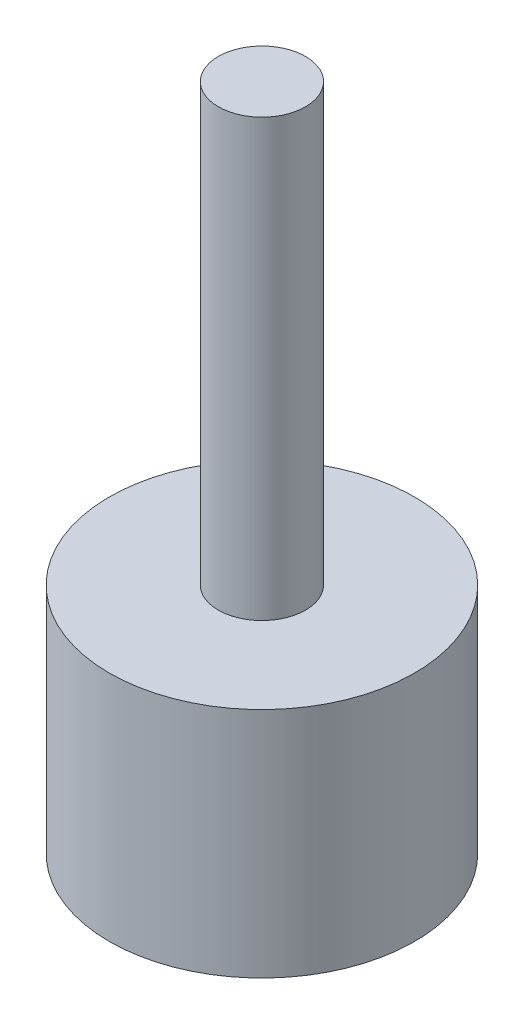
SolidWorks part; units mm, degrees
ref_plane "Front Plane" through (0, 0, 0) normal (0, 0, 1) x (1, 0, 0)
ref_plane "Top Plane" through (0, 0, 0) normal (0, 1, 0) x (1, 0, 0)
ref_plane "Right Plane" through (0, 0, 0) normal (1, 0, 0) x (0, 0, -1)
sketch "Sketch1" plane through (0, 0, 0) normal (0, 1, 0) x (1, 0, 0)
  circle A0 centre (0, 0) radius 5.25
  dimension "D1" = 10.5
extrude "Boss-Extrude1" add sketch "Sketch1" along normal blind 8
sketch "Sketch2" plane through (0, 8, 0) normal (0, 1, 0) x (1, 0, 0)
  circle A0 centre (0, 0) radius 1.5
  dimension "D1" = 3
extrude "Boss-Extrude2" add sketch "Sketch2" along normal blind 15
sketch "Sketch3" plane through (0, 0, 0) normal (0, -1, 0) x (1, 0, 0)
  line L1 (-2.5, -1.525) -> (2.5, -1.525)
  line L2 (-2.5, -1.525) -> (-2.5, 1.525)
  line L3 (-2.5, 1.525) -> (2.5, 1.525)
  line L4 (2.5, -1.525) -> (2.5, 1.525)
  line L5 (-2.5, -1.525) -> (2.5, 1.525) construction
  line L6 (-2.5, 1.525) -> (2.5, -1.525) construction
  point P1 (0, 0)
  dimension "D1" = 3.05
  dimension "D2" = 5
extrude "Cut-Extrude1" cut sketch "Sketch3" against normal blind 6
